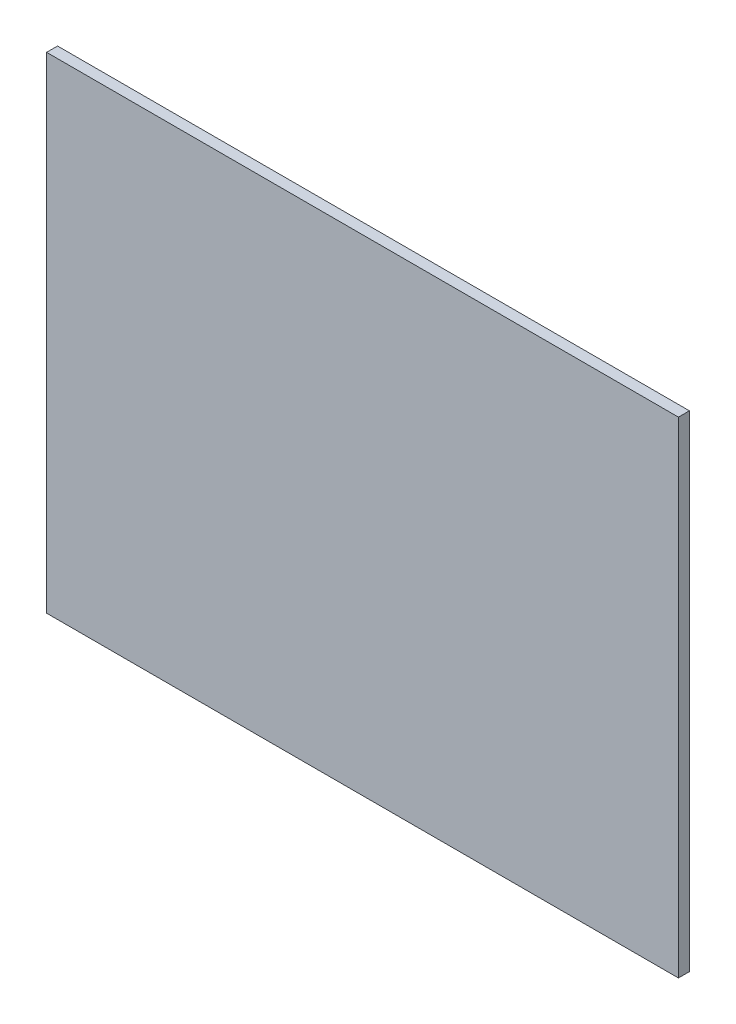
SolidWorks part; units mm, degrees
ref_plane "Plan de face" through (0, 0, 0) normal (0, 0, 1) x (1, 0, 0)
ref_plane "Plan de dessus" through (0, 0, 0) normal (0, 1, 0) x (1, 0, 0)
ref_plane "Plan de droite" through (0, 0, 0) normal (1, 0, 0) x (0, 0, -1)
sketch "Esquisse1" plane through (0, 0, 0) normal (0, 0, 1) x (1, 0, 0)
  line L1 (-38.0757, 29.0301) -> (134.9243, 29.0301)
  line L2 (-38.0757, 29.0301) -> (-38.0757, -103.9699)
  line L3 (-38.0757, -103.9699) -> (134.9243, -103.9699)
  line L4 (134.9243, 29.0301) -> (134.9243, -103.9699)
  dimension "D1" = 173
  dimension "D2" = 133
extrude "Boss.-Extru.1" add sketch "Esquisse1" along normal blind 3
equation "\"LongueurSyphon\"=170"
equation "\"D1@Esquisse1\" = \"LongueurSyphon\" + \"EpaisseurPlaque\""
equation "\"ProfondeurBoite\"=460"
equation "\"LargeurSyphon\"=120"
equation "\"EpaisseurPlaque\"= 3"
equation "\"HauteurSyphon\"=\"HauteurCoteGauche\"-\"HauteurSolSyphon\""
equation "\"D2@Esquisse1\"=\"LargeurBoite\" - \"LargeurGauche\" + \"EpaisseurPlaque\""
equation "\"HauteurCoteDroit\"= 490"
equation "\"HauteurCoteGauche\"= 540"
equation "\"HauteurSolSyphon\"= 300"
equation "\"LargeurDroite\"=10"
equation "\"LargeurGauche\"=150"
equation "\"LargeurBoite\"= \"LargeurDroite\" + \"LargeurGauche\" + \"LargeurSyphon\""
